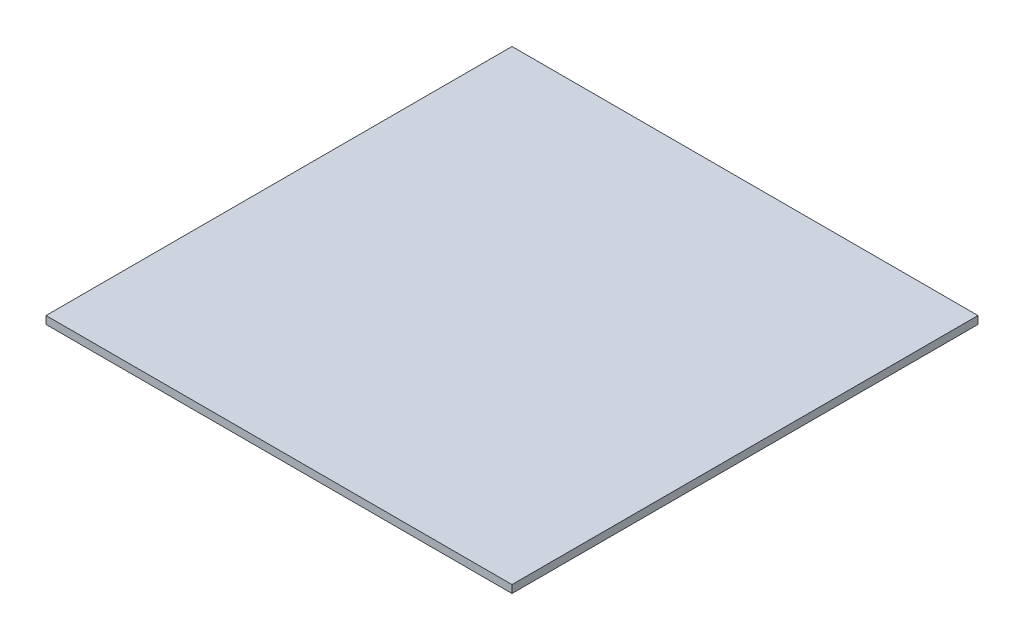
SolidWorks part; units mm, degrees
ref_plane "Front Plane" through (0, 0, 0) normal (0, 0, 1) x (1, 0, 0)
ref_plane "Top Plane" through (0, 0, 0) normal (0, 1, 0) x (1, 0, 0)
ref_plane "Right Plane" through (0, 0, 0) normal (1, 0, 0) x (0, 0, -1)
sketch3d "reference sketch"
  line L8 (-33.9558, -5, 152) -> (-33.9558, 145, 152)
  line L9 (-33.9558, 145, 152) -> (-33.9558, 145, -152.8)
  line L10 (-33.9558, 145, -152.8) -> (-33.9558, -5, -152.8)
  line L11 (-33.9558, -5, -152.8) -> (-33.9558, -5, 152)
sketch "Sketch1" plane through (0, 0, 0) normal (0, 1, 0) x (1, 0, 0)
  line L1 (-150, 150) -> (150, 150)
  line L2 (-150, 150) -> (-150, -150)
  line L3 (-150, -150) -> (150, -150)
  line L4 (150, 150) -> (150, -150)
  point P4 (0, 150)
  point P6 (-150, 0)
  dimension "D1" = 300
extrude "Boss-Extrude1" add sketch "Sketch1" along normal blind 5
ref_plane "Plane1" through (0, 0, 75) normal (0, 0, 1) x (1, 0, 0)
ref_plane "Plane2" through (0, 0, -75) normal (0, 0, -1) x (-1, 0, 0)
sketch "Sketch3" plane through (0, 0, 75) normal (0, 0, 1) x (1, 0, 0)
  line L0 (-80, 41.6164) -> (-107.5003, 5)
  line L1 (-150, 5) -> (150, 5) construction
  line L2 (-110.6095, 125.7154) -> (-72.1323, 20)
  line L3 (-33.9558, 145) -> (-33.9558, -5) construction
  point P10 (-158.3435, 131.0107)
  point P11 (-94.8244, 35.1494)
  point P12 (-76.1767, 17.3758)
  point P14 (-80, 41.6164)
  dimension "D1" = 150
  dimension "D2" = 112.5
  dimension "D3" = 70
  dimension "D4" = 80
  dimension "D5" = 15
sketch "Sketch5" plane through (0, 0, -75) normal (0, 0, -1) x (-1, 0, 0)
  line L0 (110.6095, 125.7154) -> (72.1323, 20) construction
  line L1 (80, 41.6164) -> (107.5003, 5) construction
  line L2 (110.6095, 125.7154) -> (72.1323, 20)
  line L3 (80, 41.6164) -> (107.5003, 5)
equation "\"D2@Sketch3\"=\"D1@Sketch3\"*.75"
